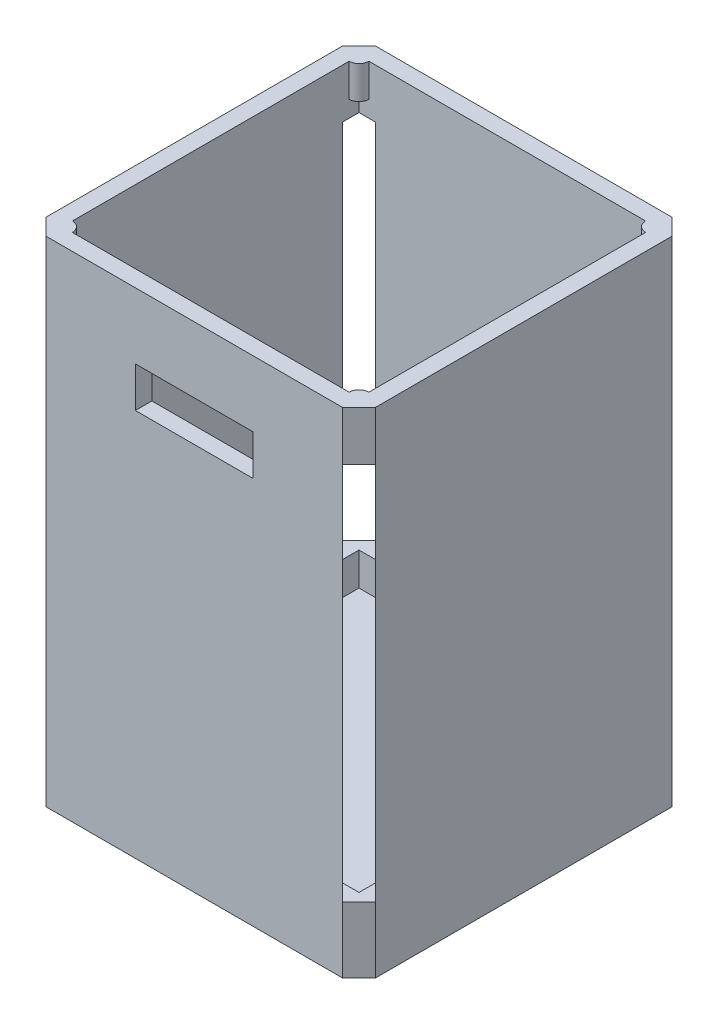
SolidWorks part; units mm, degrees
ref_plane "Front Plane" through (0, 0, 0) normal (0, 0, 1) x (1, 0, 0)
ref_plane "Top Plane" through (0, 0, 0) normal (0, 1, 0) x (1, 0, 0)
ref_plane "Right Plane" through (0, 0, 0) normal (1, 0, 0) x (0, 0, -1)
sketch "Sketch1" plane through (0, 0, 0) normal (0, 1, 0) x (1, 0, 0)
  line L1 (100, -100) -> (-100, -100)
  line L2 (100, -100) -> (100, 100)
  line L3 (100, 100) -> (-100, 100)
  line L4 (-100, -100) -> (-100, 100)
  line L5 (100, -100) -> (-100, 100) construction
  line L6 (100, 100) -> (-100, -100) construction
  point P0 (0, 0)
  dimension "D1" = 200
  dimension "D2" = 200
extrude "Boss-Extrude1" add sketch "Sketch1" along normal blind 300
sketch "Sketch2" plane through (0, 0, 0) normal (0, -1, 0) x (1, 0, 0)
  line L0 (0, 0) -> (-124.0293, 0) construction
  line L1 (0, 0) -> (0, 113.5509) construction
  line L2 (-100, -100) -> (-100, 100) construction
  line L3 (-100, 100) -> (100, 100) construction
  circle A0 centre (-90, 90) radius 2
  circle A1 centre (90, 90) radius 2
  circle A2 centre (90, -90) radius 2
  circle A3 centre (-90, -90) radius 2
  dimension "D1" = 4
  dimension "D2" = 10
  dimension "D3" = 10
extrude "Cut-Extrude1" cut sketch "Sketch2" against normal blind 15
sketch "Sketch9" plane through (0, 0, 0) normal (0, -1, 0) x (1, 0, 0)
  line L0 (0, 0) -> (0, 117.4862) construction
  line L1 (0, 0) -> (-137.1602, 0) construction
  line L2 (-84, 90) -> (84, 90)
  line L3 (90, 84) -> (90, -84)
  line L4 (84, -90) -> (-84, -90)
  line L5 (-90, -84) -> (-90, 84)
  arc A0 (-90, 84) -> (-84, 90) centre (-90, 90) ccw
  arc A1 (90, 84) -> (84, 90) centre (90, 90) cw
  arc A2 (90, -84) -> (84, -90) centre (90, -90) ccw
  arc A3 (-90, -84) -> (-84, -90) centre (-90, -90) cw
  dimension "D1" = 12
extrude "Cut-Extrude2" cut sketch "Sketch9" against normal through all from offset 20 offset against normal yes
sketch "Sketch10" plane through (0, 0, 100) normal (0, 0, 1) x (1, 0, 0)
  line L0 (0, 300) -> (0, 260) construction
  line L1 (-35.75, 260) -> (35.75, 260)
  line L2 (-35.75, 260) -> (-35.75, 235.5)
  line L3 (-35.75, 235.5) -> (35.75, 235.5)
  line L4 (35.75, 260) -> (35.75, 235.5)
  line L5 (-100, 300) -> (100, 300) construction
  line L6 (-35.75, 247.75) -> (-105.5659, 247.75) construction
  circle A0 centre (-37.75, 263.5) radius 1
  circle A1 centre (37.75, 263.5) radius 1
  circle A2 centre (37.75, 232) radius 1
  circle A3 centre (-37.75, 232) radius 1
  point P18 (0, 0)
  dimension "D4" = 2
  dimension "D1" = 71.5
  dimension "D2" = 24.5
  dimension "D3" = 40
  dimension "D5" = 3.5
  dimension "D6" = 2
extrude "Cut-Extrude4" cut sketch "Sketch10" against normal up to surface (10 mm away) contours L2 L1 L4 L3 up to face at (0, 160, 90)
chamfer "Chamfer1" distance 10 angle 45 4 edges at (100, 150, -100) (-100, 150, -100) (-100, 150, 100) (100, 150, 100)
sketch "Sketch11" plane through (0, 300, 0) normal (0, 1, 0) x (1, 0, 0)
  line L0 (90, 84) -> (90, 90)
  line L1 (90, 90) -> (84, 90)
  line L2 (84, -90) -> (90, -90)
  line L3 (90, -90) -> (90, -84)
  line L4 (-90, -84) -> (-90, -90)
  line L5 (-90, -90) -> (-84, -90)
  line L6 (-84, 90) -> (-90, 90)
  line L7 (-90, 90) -> (-90, 84)
  arc A0 (-90, 84) -> (-84, 90) centre (-90, 90) ccw construction
  arc A1 (-90, 84) -> (-84, 90) centre (-90, 90) ccw
  arc A2 (84, 90) -> (90, 84) centre (90, 90) ccw construction
  arc A3 (84, 90) -> (90, 84) centre (90, 90) ccw
  arc A4 (90, -84) -> (84, -90) centre (90, -90) ccw construction
  arc A5 (90, -84) -> (84, -90) centre (90, -90) ccw
  arc A6 (-84, -90) -> (-90, -84) centre (-90, -90) ccw construction
  arc A7 (-84, -90) -> (-90, -84) centre (-90, -90) ccw
extrude "Cut-Extrude5" cut sketch "Sketch11" against normal up to surface (280 mm away) from offset 20 contours A5 L2 L3 | A7 L4 L5 | L6 L7 A1 | L0 L1 A3 up to face at (0, 20, 0) offset against normal yes
sketch "Sketch12" plane through (95, 0, 95) normal (0.7071, 0, 0.7071) x (0.7071, 0, -0.7071)
  line L0 (7.0711, 300) -> (7.0711, 0) construction
  line L1 (7.0711, 270) -> (-7.0711, 270)
  line L2 (7.0711, 270) -> (7.0711, 40)
  line L3 (7.0711, 40) -> (-7.0711, 40)
  line L4 (-7.0711, 270) -> (-7.0711, 40)
  line L5 (-7.0711, 0) -> (-7.0711, 300) construction
  line L6 (-7.0711, 300) -> (7.0711, 300) construction
  point P10 (0, 300)
  dimension "D1" = 30
  dimension "D2" = 230
extrude "Cut-Extrude6" cut sketch "Sketch12" against normal through all
sketch "Sketch13" plane through (-95, 0, 95) normal (-0.7071, 0, 0.7071) x (0.7071, 0, 0.7071)
  line L0 (7.0711, 300) -> (7.0711, 0) construction
  line L1 (7.0711, 270) -> (-7.0711, 270)
  line L2 (7.0711, 270) -> (7.0711, 40)
  line L3 (7.0711, 40) -> (-7.0711, 40)
  line L4 (-7.0711, 270) -> (-7.0711, 40)
  line L5 (-7.0711, 0) -> (-7.0711, 300) construction
  line L6 (-7.0711, 300) -> (7.0711, 300) construction
  point P10 (0, 270)
  dimension "D1" = 30
  dimension "D2" = 230
extrude "Cut-Extrude7" cut sketch "Sketch13" against normal through all
